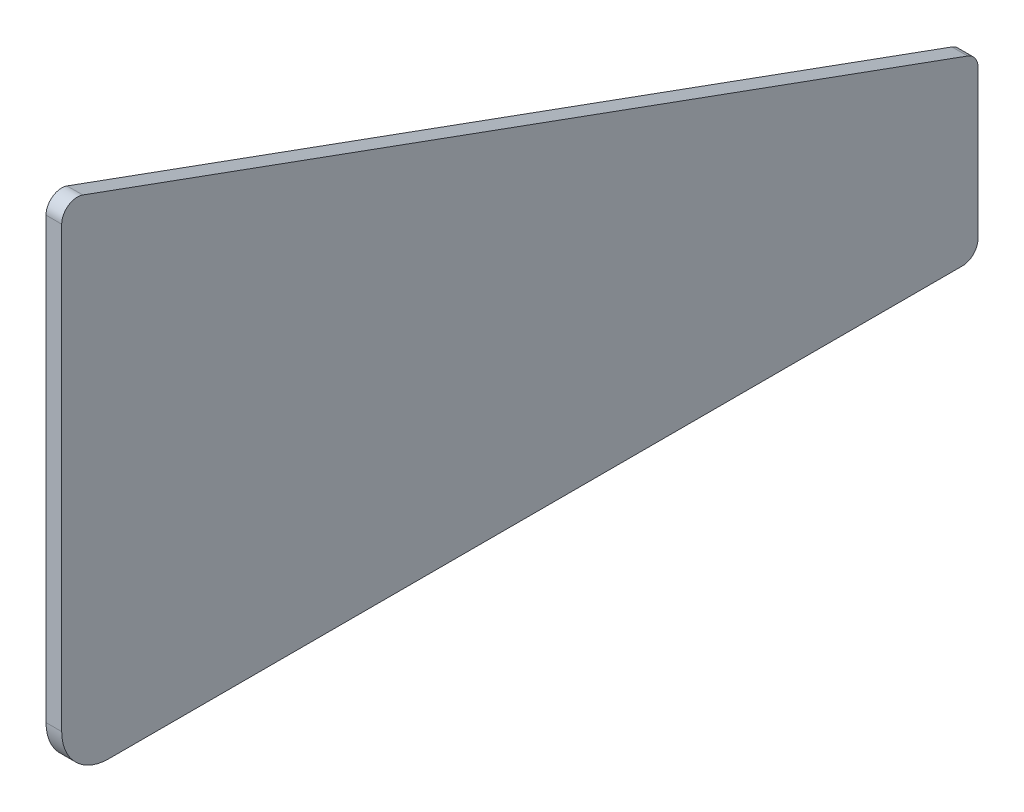
SolidWorks part; units mm, degrees
ref_plane "Front Plane" through (0, 0, 0) normal (0, 0, 1) x (1, 0, 0)
ref_plane "Top Plane" through (0, 0, 0) normal (0, 1, 0) x (1, 0, 0)
ref_plane "Right Plane" through (0, 0, 0) normal (1, 0, 0) x (0, 0, -1)
sketch "Sketch1" plane through (0, 0, 0) normal (1, 0, 0) x (0, 0, -1)
  line L0 (0, -14.2815) -> (0, -294.2815)
  line L1 (0, 29.2892) -> (0, -29.2892) construction
  line L2 (30, -324.2815) -> (573.8156, -324.2815)
  line L3 (583.8156, -314.2815) -> (583.8156, -219.4936)
  line L4 (577.2358, -210.0966) -> (13.4202, -4.8846)
  arc A0 (30, -324.2815) -> (0, -294.2815) centre (30, -294.2815) cw
  arc A1 (573.8156, -324.2815) -> (583.8156, -314.2815) centre (573.8156, -314.2815) ccw
  arc A2 (583.8156, -219.4936) -> (577.2358, -210.0966) centre (573.8156, -219.4936) ccw
  arc A3 (13.4202, -4.8846) -> (0, -14.2815) centre (10, -14.2815) ccw
  point P9 (0, -324.2815)
  point P16 (0, 0)
  dimension "D2" = 30
  dimension "D3" = 10
  dimension "D1" = 70
  dimension "D4" = 280
  dimension "D5" = 600
extrude "Boss-Extrude1" add sketch "Sketch1" along normal blind 10
sketch "Sketch2" plane through (10, 0, 0) normal (1, 0, 0) x (0, 0, -1)
  arc A0 (23.1622, -218.0173) -> (26.7381, -200.3183) centre (26.5742, -209.4959) cw
  arc A1 (549.474, -291.831) -> (546.1549, -257.731) centre (546.1581, -274.9423) ccw
  arc A2 (26.9502, -47.7372) -> (35.1249, -39.1544) centre (32.8168, -45.1404) cw
  arc A3 (356.3201, -205.3163) -> (353.1695, -171.1817) centre (353.1695, -188.3944) ccw
  spline S0 degree 3 poles (23.1622, -218.0173) (143.0808, -266.0342) (284.6699, -324.5722) (474.7501, -306.5023) (549.474, -291.831) knots 0 0 0 0 0.576112 1 1 1 1
  spline S1 degree 3 poles (26.7381, -200.3183) (45.9144, -200.6608) (151.3211, -255.5104) (414.8803, -286.3851) (542.4311, -257.7317) (546.1549, -257.731) knots 0 0 0 0 0.560935 0.660935 1 1 1 1
  spline S2 degree 3 poles (26.9502, -47.7372) (35.3127, -66.6296) (121.3965, -217.9891) (352.8389, -205.9644) (356.3201, -205.3163) knots 0 0 0 0 0.590315 1 1 1 1
  spline S3 degree 3 poles (35.1249, -39.1544) (50.603, -45.1224) (99.0425, -170.6619) (331.224, -171.1817) (353.1695, -171.1817) knots 0 0 0 0 0.639196 1 1 1 1
  point P13 (39.6682, -52.7841)
  point P14 (220.1955, -195.0198)
  point P15 (358.3924, -192.1615)
  point P18 (360.8634, -218.9461)
  point P20 (203.6071, -219.6946)
  point P21 (0, 0)
  point P22 (210.1401, -175.2683)
  point P23 (0, 0)
  point P24 (0, 0)
  point P25 (0, 0)
  point P26 (353.1695, -171.1817)
  point P27 (187.5993, -154.5316)
  point P28 (199.8551, -188.3944)
  point P29 (26.9502, -47.7372)
  point P30 (0, 0)
  point P31 (26.1508, -205.3163)
  point P32 (23.1622, -198.66)
  point P33 (26.9887, -198.1668)
  point P34 (187.5993, -188.3944)
  point P35 (322.3175, -274.9423)
  point P36 (25.6108, -205.3163)
  point P37 (26.5509, -200.4381)
  point P38 (0, 0)
  point P39 (0, 0)
  point P40 (26.5742, -200.3183)
sketch "Sketch3" plane through (0, 0, 0) normal (-1, 0, 0) x (0, 0, 1)
  arc A2 (-23.1622, -218.0173) -> (-26.7381, -200.3183) centre (-26.5742, -209.4959) ccw
  arc A3 (-546.1549, -257.731) -> (-549.474, -291.831) centre (-546.1581, -274.9423) ccw
  arc A4 (-23.1622, -218.0173) -> (-26.7381, -200.3183) centre (-26.5742, -209.4959) ccw
  arc A5 (-546.1549, -257.731) -> (-549.474, -291.831) centre (-546.1581, -274.9423) ccw
  arc A6 (-26.9502, -47.7372) -> (-35.1249, -39.1544) centre (-32.8168, -45.1404) ccw
  arc A7 (-353.1695, -171.1817) -> (-356.3201, -205.3163) centre (-353.1695, -188.3944) ccw
  arc A8 (-26.9502, -47.7372) -> (-35.1249, -39.1544) centre (-32.8168, -45.1404) ccw
  arc A9 (-353.1695, -171.1817) -> (-356.3201, -205.3163) centre (-353.1695, -188.3944) ccw
  spline S2 degree 3 poles (-2896.6142, -4288.4219) (3.574, 379.1035) (337.9044, -198.2) (-671.2842, -316.4215) (-1165.7534, 76.4704) (4167.8421, -1921.4128) knots -1.856226 -1.856226 -1.856226 -1.856226 0.560935 0.660935 1.972851 1.972851 1.972851 1.972851 only from (-26.7381, -200.3183) to (-546.1549, -257.731)
  spline S3 degree 3 poles (4297.6783, -1440.9535) (-2101.1476, 528.1742) (-39.3944, -1013.16) (229.8904, 277.3112) (4925.3757, 333.413) knots -3.073366 -3.073366 -3.073366 -3.073366 0.423888 3.006514 3.006514 3.006514 3.006514 only from (-549.474, -291.831) to (-23.1622, -218.0173)
  spline S4 degree 3 poles (-26.7381, -200.3183) (-45.9144, -200.6608) (-151.3211, -255.5104) (-414.8803, -286.3851) (-542.4311, -257.7317) (-546.1549, -257.731) knots 0 0 0 0 0.560935 0.660935 1 1 1 1
  spline S5 degree 3 poles (-549.474, -291.831) (-474.7501, -306.5023) (-284.6699, -324.5722) (-143.0808, -266.0342) (-23.1622, -218.0173) knots 0 0 0 0 0.423888 1 1 1 1
  spline S6 degree 3 poles (1154.6406, -4892.5213) (-500.1842, 847.1931) (679.6519, -597.1648) (-1151.2382, 7.0013) (4611.9466, -753.8783) knots -1.849916 -1.849916 -1.849916 -1.849916 0.639196 2.198 2.198 2.198 2.198 only from (-35.1249, -39.1544) to (-353.1695, -171.1817)
  spline S7 degree 3 poles (4570.7768, -1047.92) (-1095.3741, 46.8314) (476.6072, -749.5305) (-175.5635, 954.0689) (-848.8771, -4973.4503) knots -1.172462 -1.172462 -1.172462 -1.172462 0.409685 2.739203 2.739203 2.739203 2.739203 only from (-356.3201, -205.3163) to (-26.9502, -47.7372)
  spline S8 degree 3 poles (-35.1249, -39.1544) (-50.603, -45.1224) (-99.0425, -170.6619) (-331.224, -171.1817) (-353.1695, -171.1817) knots 0 0 0 0 0.639196 1 1 1 1
  spline S9 degree 3 poles (-356.3201, -205.3163) (-352.8389, -205.9644) (-121.3965, -217.9891) (-35.3127, -66.6296) (-26.9502, -47.7372) knots 0 0 0 0 0.409685 1 1 1 1
  dimension "D1" = 0
  dimension "D2" = 0
extrude "Cut-Extrude3" cut sketch "Sketch3" against normal blind 3
